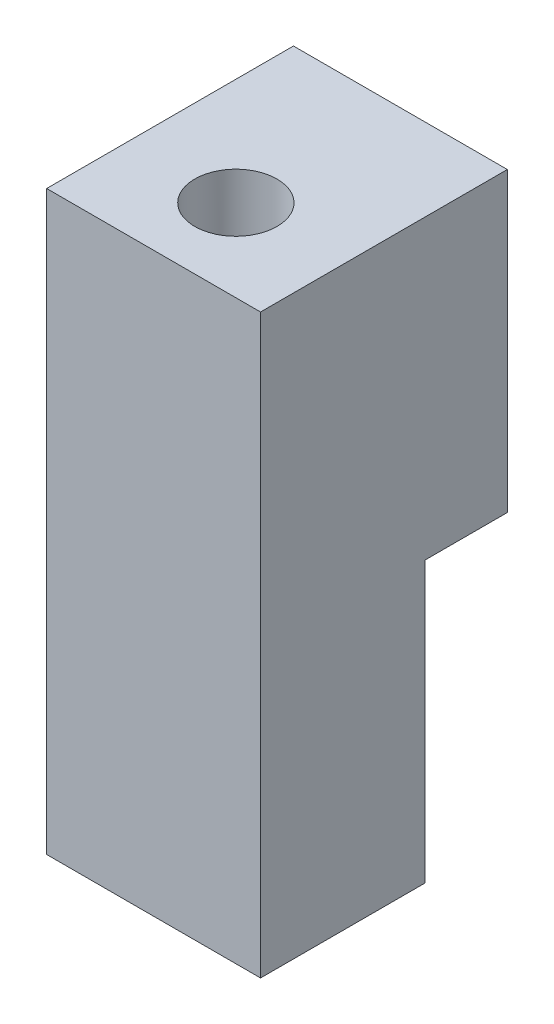
SolidWorks part; units mm, degrees
ref_plane "Front Plane" through (0, 0, 0) normal (0, 0, 1) x (1, 0, 0)
ref_plane "Top Plane" through (0, 0, 0) normal (0, 1, 0) x (1, 0, 0)
ref_plane "Right Plane" through (0, 0, 0) normal (1, 0, 0) x (0, 0, -1)
sketch "Sketch2" plane through (0, 0, 0) normal (0, 0, 1) x (1, 0, 0)
  line L0 (125.75, 12.9444) -> (138.75, 12.9444) construction
  line L5 (125.45, -3.5556) -> (138.75, -3.5556)
  line L6 (138.75, -3.5556) -> (138.75, 35)
  line L7 (138.75, 35) -> (125.75, 35)
  line L8 (125.75, 35) -> (125.75, 5.0019)
  line L9 (125.45, 3.05) -> (125.45, -3.5556)
  line L10 (125.45, -3.5556) -> (138.75, -3.5556) construction
  line L11 (138.75, 12.9444) -> (138.75, 35)
  line L12 (138.75, 35) -> (125.75, 35)
  line L13 (125.75, 35) -> (125.75, 12.9444)
  arc A0 (138.75, 12.9444) -> (125.75, 12.9444) centre (132.25, 12.9444) ccw
  arc A1 (125.75, 5.0019) -> (125.45, 3.05) centre (131.95, 3.05) ccw
  point P8 (132.25, 12.9444)
  dimension "D2" = 16.5
  dimension "D1" = 0
extrude "Boss-Extrude1" add sketch "Sketch2" along normal blind 10
sketch "Sketch3" plane through (0, 35, 0) normal (0, 1, 0) x (1, 0, 0)
  line L0 (138.75, -5) -> (125.75, -5)
  line L1 (138.75, -10) -> (138.75, 0) construction
  line L2 (125.75, -10) -> (125.75, 0) construction
  line L4 (138.75, -5) -> (125.75, -5)
  line L5 (138.75, -5) -> (138.75, -10)
  line L6 (138.75, -10) -> (125.75, -10)
  line L7 (125.75, -5) -> (125.75, -10)
  line M2 (125.75, 0) -> (125.75, -10)
  line M3 (125.75, -10) -> (138.75, -10)
  line M4 (138.75, -10) -> (138.75, 0)
extrude "Boss-Extrude2" add sketch "Sketch3" against normal up to vertex (22.0556 mm away) contours L0 M4 M2 M3 region at (132.25, 35, 7.5) up to point (138.75, 12.9444, 10)
sketch "Sketch4" plane through (0, 35, 0) normal (0, 1, 0) x (1, 0, 0)
  line L0 (125.75, 0) -> (125.75, -24) construction
  line L1 (138.75, -10) -> (125.75, -10)
  line L2 (138.75, -10) -> (138.75, -15)
  line L3 (138.75, -15) -> (125.75, -15)
  line L4 (125.75, -10) -> (125.75, -15)
  dimension "D1" = 5
extrude "Boss-Extrude3" add sketch "Sketch4" against normal up to vertex (22.0556 mm away) up to point (138.75, 12.9444, 10)
sketch "Sketch5" plane through (0, 12.9444, 0) normal (0, -1, 0) x (1, 0, 0)
  line L0 (125.75, 15) -> (138.75, 5) construction
  circle A0 centre (132.25, 10) radius 2.5
  dimension "D1" = 5
extrude "Cut-Extrude1" cut sketch "Sketch5" against normal blind 23
sketch "Sketch6" plane through (0, 12.9444, 0) normal (0, -1, 0) x (1, 0, 0)
  line L0 (138.75, 15) -> (138.75, 5) construction
  line L1 (125.75, 8.5) -> (138.75, 8.5)
  line L2 (125.75, 8.5) -> (125.75, 11.5)
  line L3 (125.75, 11.5) -> (138.75, 11.5)
  line L4 (138.75, 8.5) -> (138.75, 11.5)
  line L5 (125.75, 8.5) -> (138.75, 11.5) construction
  line L6 (125.75, 11.5) -> (138.75, 8.5) construction
  line L7 (127.25, 11.5) -> (127.25, 8.5)
  line L8 (137.25, 11.5) -> (137.25, 8.5)
  point P0 (132.25, 10)
  circle M4 centre (132.25, 10) radius 2.5
  dimension "D1" = 3
  dimension "D2" = 5
  dimension "D3" = 5
extrude "Cut-Extrude2" cut sketch "Sketch6" against normal offset from surface (17.0556 mm away) 5 contours L8 L3 L1 M4 | L3 L7 L1 M4 region at (128.5837, 12.9444, 10) region at (135.9163, 12.9444, 10) up to face at (132.25, 35, 7.5)
sketch "Sketch7" plane through (0, 12.9444, 0) normal (0, -1, 0) x (1, 0, 0)
  line L0 (132.25, 10) -> (132.25, 5)
  line L1 (131, 10) -> (133.5, 10)
  line L2 (131, 5) -> (133.5, 5)
  line L3 (133.5, 10) -> (133.5, 5)
  line L4 (138.75, 5) -> (125.75, 5) construction
  line L5 (131, 10) -> (131, 5)
  line M8 (125.75, 5) -> (138.75, 5)
  arc M12 (134.25, 8.5) -> (130.25, 8.5) centre (132.25, 10) cw
  dimension "D1" = 1.25
extrude "Cut-Extrude3" cut sketch "Sketch7" against normal blind 5 contours L5 L0 M12 M8 | L3 L0 M12 M8 region at (132.8882, 12.9444, 6.3061) region at (131.6118, 12.9444, 6.3061)
sketch "Sketch8" plane through (0, 12.9444, 0) normal (0, -1, 0) x (1, 0, 0)
  line L13 (133.5, 7.8349) -> (133.5, 5)
  line L14 (133.5, 5) -> (138.75, 5)
  line L15 (138.75, 5) -> (138.75, 15)
  line L16 (138.75, 15) -> (125.75, 15)
  line L17 (125.75, 15) -> (125.75, 5)
  line L18 (125.75, 5) -> (131, 5)
  line L19 (131, 5) -> (131, 7.8349)
  line L20 (130.25, 8.5) -> (127.25, 8.5)
  line L21 (127.25, 8.5) -> (127.25, 11.5)
  line L22 (127.25, 11.5) -> (130.25, 11.5)
  line L23 (134.25, 11.5) -> (137.25, 11.5)
  line L24 (137.25, 11.5) -> (137.25, 8.5)
  line L25 (137.25, 8.5) -> (134.25, 8.5)
  line L26 (133.5, 7.8349) -> (133.5, 5)
  line L27 (133.5, 5) -> (138.75, 5)
  line L28 (138.75, 5) -> (138.75, 15)
  line L29 (138.75, 15) -> (125.75, 15)
  line L30 (125.75, 15) -> (125.75, 5)
  line L31 (125.75, 5) -> (131, 5)
  line L32 (131, 5) -> (131, 7.8349)
  line L33 (130.25, 8.5) -> (127.25, 8.5)
  line L34 (127.25, 8.5) -> (127.25, 11.5)
  line L35 (127.25, 11.5) -> (130.25, 11.5)
  line L36 (134.25, 11.5) -> (137.25, 11.5)
  line L37 (137.25, 11.5) -> (137.25, 8.5)
  line L38 (137.25, 8.5) -> (134.25, 8.5)
  arc A3 (130.25, 8.5) -> (131, 7.8349) centre (132.25, 10) ccw
  arc A4 (134.25, 11.5) -> (130.25, 11.5) centre (132.25, 10) ccw
  arc A5 (133.5, 7.8349) -> (134.25, 8.5) centre (132.25, 10) ccw
  arc A6 (130.25, 8.5) -> (131, 7.8349) centre (132.25, 10) ccw
  arc A7 (134.25, 11.5) -> (130.25, 11.5) centre (132.25, 10) ccw
  arc A8 (133.5, 7.8349) -> (134.25, 8.5) centre (132.25, 10) ccw
  dimension "D1" = 0
extrude "Boss-Extrude4" add sketch "Sketch8" along normal blind 13
sketch "Sketch10" plane through (0, -0.0556, 0) normal (0, -1, 0) x (1, 0, 0)
  line L0 (125.75, 5) -> (125.75, 0) construction
  line L5 (138.75, 5) -> (138.75, 0) construction
  line L6 (125.75, 5) -> (125.75, 0)
  line L7 (138.75, 5) -> (138.75, 0)
  line L9 (125.75, 5) -> (138.75, 5)
  line L10 (125.75, 5) -> (125.75, 0)
  line L11 (125.75, 0) -> (138.75, 0)
  line L12 (138.75, 5) -> (138.75, 0)
  line M3 (133.5, 5) -> (138.75, 5)
  line M7 (125.75, 5) -> (131, 5)
extrude "Cut-Extrude4" cut sketch "Sketch10" against normal blind 17 contours L6 L11 L7 L9 M3 M7 region at (132.25, -0.0556, 2.5)
